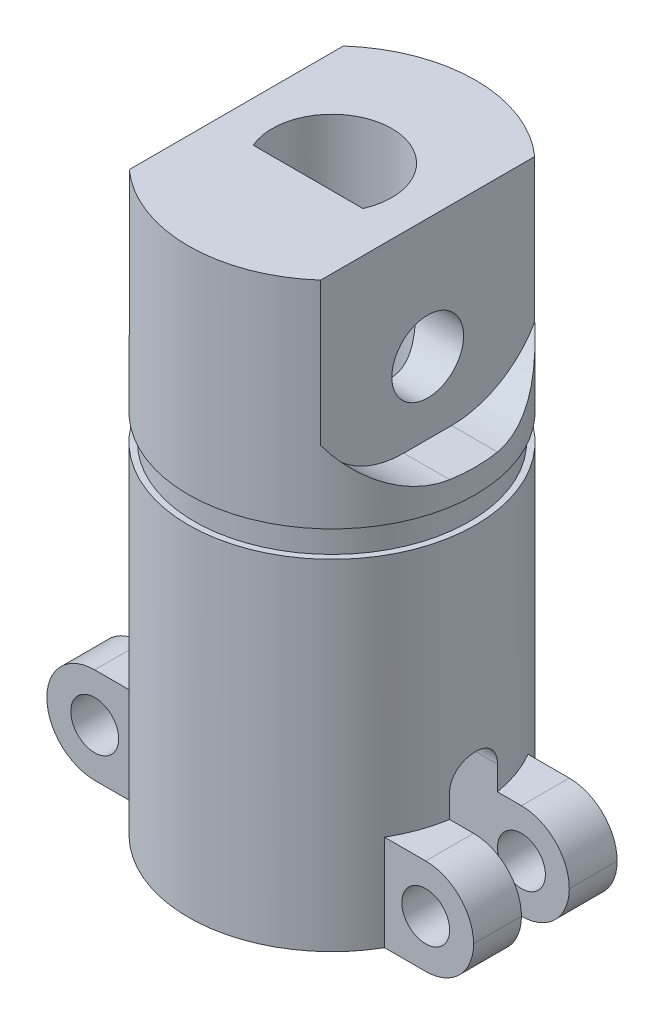
SolidWorks part; units mm, degrees
material "Polyetheretherketone (PEEK)"
ref_plane "Front Plane" through (0, 0, 0) normal (0, 0, 1) x (1, 0, 0)
ref_plane "Top Plane" through (0, 0, 0) normal (0, 1, 0) x (1, 0, 0)
ref_plane "Right Plane" through (0, 0, 0) normal (1, 0, 0) x (0, 0, -1)
sketch "Sketch2" plane through (0, 0, 0) normal (0, 0, 1) x (1, 0, 0)
  line L0 (0, 0) -> (0, 26.1) construction
  line L19 (0, 26.1) -> (-6, 26.1)
  line L20 (-6, 26.1) -> (-6, 17.1)
  line L21 (-6, 17.1) -> (-5.75, 17.1)
  line L22 (-5.75, 17.1) -> (-5.75, 16)
  line L23 (-5.75, 16) -> (-6, 16)
  line L24 (-6, 16) -> (-6, 4)
  line L25 (-6, 4) -> (-8, 4)
  line L26 (-8, 4) -> (-8, 0)
  line L27 (-8, 0) -> (-7, 0)
  line L28 (-7, 0) -> (-7, 1.8)
  line L29 (-7, 1.8) -> (0, 1.8)
  line L31 (0, 1.8) -> (0, 26.1)
  line L40 (-6, 4) -> (-10.5, 4) construction
  line L41 (-6, 4) -> (-6, 9) construction
  line L42 (-6, 9) -> (-10.5, 9) construction
  line L43 (-10.5, 4) -> (-10.5, 9) construction
  line L44 (-6, 16) -> (-10.5, 16) construction
  line L45 (-6, 16) -> (-6, 11) construction
  line L46 (-6, 11) -> (-10.5, 11) construction
  line L47 (-10.5, 16) -> (-10.5, 11) construction
  dimension "D1" = 12
  dimension "D2" = 10.5
  dimension "D3" = 5
  dimension "D4" = 5
  dimension "D5" = 16
  dimension "D6" = 14
  dimension "D8" = 1.8
  dimension "D9" = 1.1
  dimension "D10" = 11.5
  dimension "D11" = 9
  dimension "D12" = 4
  dimension "D13" = 12
revolve "Revolve1" add sketch "Sketch2" angle 360 about L0
ref_plane "Plane1" through (-6, 0, 0) normal (-1, 0, 0) x (0, 0, 1)
sketch "Sketch3" plane through (-6, 0, 0) normal (-1, 0, 0) x (0, 0, 1)
  line L0 (0, 26.1) -> (0, 9.9472) construction
  line L1 (6, 26.1) -> (-6, 26.1) construction
  line L2 (9, 26.1) -> (-9, 26.1)
  line L3 (-1, 18.1) -> (1, 18.1)
  arc A0 (-9, 26.1) -> (-5, 22.1) centre (-9, 22.1) cw
  arc A1 (-5, 22.1) -> (-1, 18.1) centre (-1, 22.1) ccw
  arc A2 (9, 26.1) -> (5, 22.1) centre (9, 22.1) ccw
  arc A3 (5, 22.1) -> (1, 18.1) centre (1, 22.1) cw
  point P13 (0, 18.1)
  dimension "D1" = 1
  dimension "D2" = 8
  dimension "D3" = 4
  dimension "D4" = 4
  dimension "D5" = 8
extrude "Cut-Extrude2" cut sketch "Sketch3" against normal blind 2 contours A0 A1 L3 A3 A2 L2
mirror "Mirror1" about plane through (0, 0, 0) normal (1, 0, 0) of "Cut-Extrude2"
sketch "Sketch4" plane through (-4, 0, 0) normal (-1, 0, 0) x (0, 0, 1)
  line L0 (1, 18.1) -> (-1, 18.1) construction
  circle A0 centre (0, 21.1) radius 1.5
  point P5 (0, 18.1)
  dimension "D1" = 3
  dimension "D2" = 3
extrude "Cut-Extrude3" cut sketch "Sketch4" against normal through all contours A0
sketch "Sketch5" plane through (0, 1.8, 0) normal (0, -1, 0) x (1, 0, 0)
  line L0 (-2.2913, 1) -> (2.2913, 1)
  circle A0 centre (0, 0) radius 2.5
  dimension "D1" = 5
  dimension "D2" = 1
extrude "Cut-Extrude4" cut sketch "Sketch5" against normal through all contours L0 A0 region at (0, 1.8, -0.5463)
sketch "Sketch6" plane through (0, 4, 0) normal (0, 1, 0) x (1, 0, 0)
  circle A0 centre (0, 0) radius 6
  circle A1 centre (0, 0) radius 8
  circle A2 centre (0, 0) radius 8
  dimension "D1" = 0
extrude "Cut-Extrude5" cut sketch "Sketch6" against normal blind 10
ref_plane "Plane2" through (6, 0, 0) normal (1, 0, 0) x (0, 0, -1)
sketch "Sketch7" plane through (6, 0, 0) normal (1, 0, 0) x (0, 0, -1)
  line L0 (-1, 1.8) -> (2.5, 1.8) construction
  line L1 (-1, 1.8) -> (2.5, 1.8) construction
  line L2 (-1, 1.8) -> (-1, 6.8)
  line L3 (1, 6.8) -> (1, 1.8)
  line L4 (1, 1.8) -> (-1, 1.8)
  arc A0 (-1, 6.8) -> (1, 6.8) centre (0, 6.8) cw
  dimension "D1" = 1
  dimension "D2" = 5
extrude "Cut-Extrude6" cut sketch "Sketch7" against normal through all
sketch "Sketch8" plane through (0, 1.8, 0) normal (0, -1, 0) x (1, 0, 0)
  line L0 (5.9161, 1) -> (8.9161, 1)
  line L1 (8.9161, 1) -> (8.9161, 3)
  line L2 (8.9161, 3) -> (5.1962, 3)
  line L3 (0, 0) -> (0, -6.6764) construction
  line L4 (5.9161, -1) -> (8.9161, -1)
  line L5 (8.9161, -1) -> (8.9161, -3)
  line L6 (8.9161, -3) -> (5.1962, -3)
  line L7 (-8.9161, -3) -> (-5.1962, -3)
  line L8 (-8.9161, -1) -> (-8.9161, -3)
  line L9 (-5.9161, -1) -> (-8.9161, -1)
  line L10 (-8.9161, 3) -> (-5.1962, 3)
  line L11 (-8.9161, 1) -> (-8.9161, 3)
  line L12 (-5.9161, 1) -> (-8.9161, 1)
  arc A0 (5.9161, 1) -> (-5.9161, 1) centre (0, 0) ccw construction
  arc A1 (5.9161, 1) -> (5.1962, 3) centre (0, 0) ccw
  arc A2 (-5.9161, -1) -> (5.9161, -1) centre (0, 0) ccw construction
  arc A3 (-5.1962, -3) -> (-5.9161, -1) centre (0, 0) cw
  arc A4 (5.1962, -3) -> (5.9161, -1) centre (0, 0) ccw
  arc A5 (-5.9161, 1) -> (-5.1962, 3) centre (0, 0) cw
  arc M10 (5.9161, 1) -> (-5.9161, 1) centre (0, 0) ccw
  dimension "D1" = 2
  dimension "D2" = 2
  dimension "D3" = 3
extrude "Boss-Extrude1" add sketch "Sketch8" against normal blind 4 contours L7 A3 L9 L8 | L12 L10 L11 M10 | L1 L2 L0 M10 | A4 L6 L5 L4 region at (7.2632, 1.8, 2.0362) region at (-7.2632, 1.8, 2.0362) region at (7.2632, 1.8, -2.0362) region at (-7.2632, 1.8, -2.0362)
sketch "Sketch9" plane through (0, 0, -3) normal (0, 0, -1) x (-1, 0, 0)
  line L0 (-8.9161, 5.8) -> (-8.9161, 1.8) construction
  line L1 (0, 0) -> (0, -2.3881) construction
  circle A0 centre (-6.9161, 3.8) radius 1
  circle A1 centre (6.9161, 3.8) radius 1
  point P4 (-8.9161, 3.8)
  dimension "D1" = 2
  dimension "D2" = 2
extrude "Cut-Extrude7" cut sketch "Sketch9" against normal through all
fillet "Fillet1" radius 2 8 edges at (-8.9161, 5.8, 2) (-8.9161, 1.8, 2) (-8.9161, 1.8, -2) (-8.9161, 5.8, -2) (8.9161, 1.8, 2) (8.9161, 5.8, 2) (8.9161, 1.8, -2) (8.9161, 5.8, -2)
